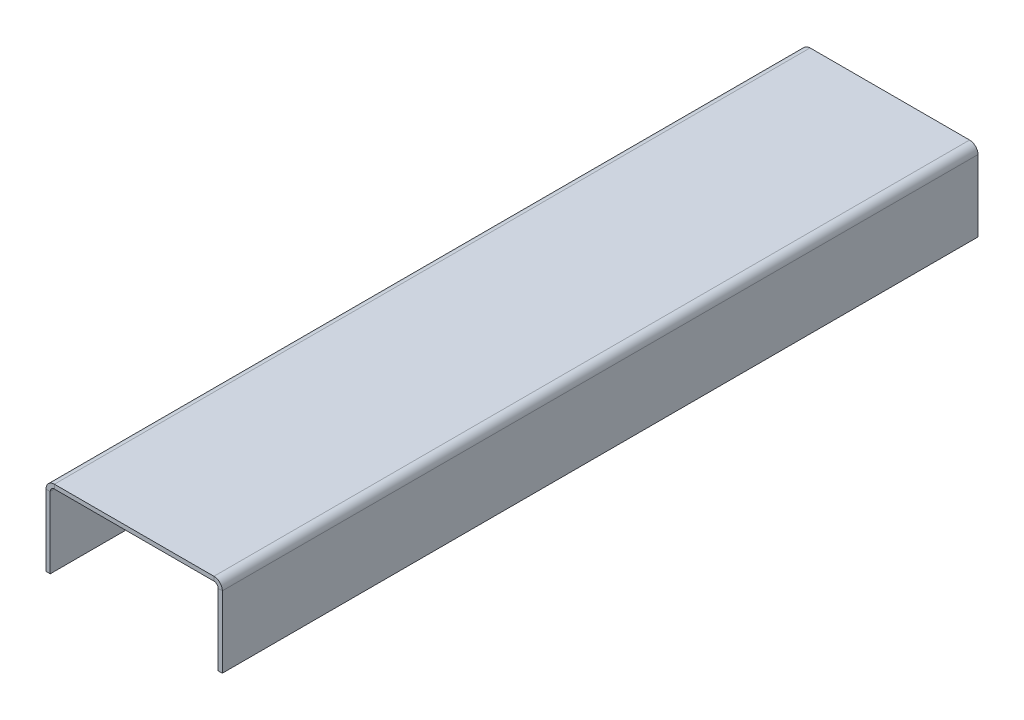
SolidWorks part; units mm, degrees
note: The reader was unsure of these and kept them because the rebuilt part matched: thickness of "Base-Flange1", "Edge-Flange1", "Sheet-Metal1", "Sheet-Metal2"; flange length of "Edge-Flange1".
material "6061 Alloy"
ref_plane "Front Plane" through (0, 0, 0) normal (0, 0, 1) x (1, 0, 0)
ref_plane "Top Plane" through (0, 0, 0) normal (0, 1, 0) x (1, 0, 0)
ref_plane "Right Plane" through (0, 0, 0) normal (1, 0, 0) x (0, 0, -1)
sketch "Front View Skeleton" plane through (0, 0, 0) normal (0, 0, 1) x (1, 0, 0)
  line L0 (-40, 240) -> (40, 240)
  line L1 (40, 240) -> (42, 240)
  line L2 (42, 240) -> (42, 30)
  line L3 (42, 30) -> (40, 30)
  line L4 (40, 30) -> (40, 240)
  line L5 (40, 240) -> (40, 242)
  line L6 (40, 242) -> (-40, 242)
  line L7 (0, 242) -> (0, 240) construction
  line L8 (0, 240) -> (0, 0) construction
  line L9 (-40, 240) -> (-40, 242)
  line L10 (-40, 30) -> (-40, 240)
  line L11 (-42, 30) -> (-40, 30)
  line L12 (-42, 240) -> (-42, 30)
  line L13 (-40, 240) -> (-42, 240)
  line L14 (42, 30) -> (42, 28)
  line L38 (34.8453, 358) -> (100, 245.1487)
  line L39 (-36, 360) -> (36, 360)
  line L41 (-34.8453, 358) -> (34.8453, 358)
  line L43 (-36, 360) -> (34.8453, 358) construction
  line L44 (-34.8453, 358) -> (36, 360) construction
  line L45 (232.6917, 28) -> (232.6917, 388) construction
  line L46 (36, 360) -> (36.5774, 359)
  line L47 (101.7321, 246.1487) -> (36.5774, 359)
  line L50 (42, 28) -> (96, 28)
  line L51 (-101.7321, 246.1487) -> (-36.5774, 359)
  line L52 (-34.8453, 358) -> (-100, 245.1487)
  line L53 (96, 28) -> (100, 28)
  line L54 (100, 28) -> (100, 46)
  line L55 (100, 46) -> (98, 46)
  line L56 (98, 46) -> (98, 30)
  line L58 (0, 358) -> (0, 360) construction
  line L59 (-36.5774, 359) -> (-36, 360)
  line L60 (-101.7321, 246.1487) -> (-100, 245.1487) construction
  line L66 (98, 30) -> (42, 30)
  line L72 (-42, 30) -> (-42, 28)
  line L73 (101.7321, 246.1487) -> (102, 245.6846)
  line L74 (-102, 245.6846) -> (-101.7321, 246.1487)
  line L75 (34.8453, 358) -> (36.5774, 359) construction
  line L77 (100, 28) -> (100, 245.1487)
  line L81 (-98, 30) -> (-42, 30)
  line L82 (-98, 46) -> (-98, 30)
  line L83 (-100, 46) -> (-98, 46)
  line L84 (-100, 28) -> (-100, 46)
  line L85 (-96, 28) -> (-100, 28)
  line L86 (-42, 28) -> (-96, 28)
  line L87 (100, 28) -> (102, 28)
  line L88 (-100, 28) -> (-97.9629, 28)
  line L89 (102, 245.6846) -> (102, 28)
  line L90 (-102, 245.6846) -> (-102, 28)
  line L91 (-100, 28) -> (-100, 245.1487)
  line L92 (-100, 28) -> (-102, 28)
  point P33 (0, 358.9837)
ref_plane "Plane1" through (0, 240, 0) normal (0, 1, 0) x (1, 0, 0)
sketch "Sketch1" plane through (0, 240, 0) normal (0, 1, 0) x (1, 0, 0)
  line L1 (-40, 180) -> (40, 180)
  line L2 (-40, 180) -> (-40, -180)
  line L3 (-40, -180) -> (40, -180)
  line L4 (40, 180) -> (40, -180)
  line L5 (-40, 180) -> (40, -180) construction
  line L6 (-40, -180) -> (40, 180) construction
  point P0 (0, 0)
base flange "Base-Flange1" sketch "Sketch1" thickness 2 reverse thickness direction yes parameters "D1"=2
edge flange "Edge-Flange1" sketch "Sketch8" flange profiles "Sketch8", "Sketch10" flange angle 90 flange length 36 flange position material outside bend radius 2 thickness 2 relief obround parameters "D6"=10, "D8"=1
sketch "Sketch8" plane through (40, 240, 0) normal (1, 0, 0) x (0, 0, 1)
  line L2 (-180, 0) -> (-180, 36)
  line L3 (-180, 36) -> (180, 36)
  line L4 (180, 36) -> (180, 0)
  line L11 (180, 0) -> (-180, 0) construction
  line L12 (180, 0) -> (-180, 0)
sketch "Sketch10" plane through (-40, 240, 0) normal (-1, 0, 0) x (0, 0, -1)
  line L2 (-180, 0) -> (-180, 36)
  line L3 (-180, 36) -> (180, 36)
  line L4 (180, 36) -> (180, 0)
  line L11 (180, 0) -> (-180, 0) construction
  line L12 (180, 0) -> (-180, 0)
bend "EdgeBend1" bend radius 2 bend angle 90 parameters "D5"=1
bend "EdgeBend2" bend radius 2 bend angle 90 parameters "D5"=3
sketch "Bend-Lines1" [suppressed] plane through (0, 0, 0) normal (0, 1, 0) x (1, 0, 0)
sketch "Bounding-Box1" [suppressed] plane through (0, 0, 0) normal (0, 1, 0) x (1, 0, 0)
sheet metal parameters "Sheet-Metal1" thickness 2 parameters "D1"=2
flat pattern "Flat-Pattern1" [suppressed]
sketch "Bend-Lines2" plane through (0, 0, 0) normal (0, 1, 0) x (1, 0, 0)
sketch3d "Bounding-Box2" [suppressed]
  line L0 (40, 180, 0) -> (40, -180, 0) construction
  line L1 (-40, 180, 0) -> (-40, -180, 0) construction
  line L2 (40, 180, 0) -> (-40, 180, 0) construction
  line L3 (40, -180, 0) -> (-40, -180, 0) construction
sheet metal parameters "Sheet-Metal2" thickness 2 parameters "D1"=2, "D7"=3
flat pattern "Flat-Pattern1"
sketch "Bend-Lines2" plane through (0, 240, 0) normal (0, -1, 0) x (-1, 0, 0)
  line L0 (-40.3562, 180) -> (-40.3562, -180) construction
  line L1 (-40.3562, 180) -> (-40.3562, -180) construction
  line L2 (40.3562, -180) -> (40.3562, 180) construction
  line L3 (40.3562, -180) -> (40.3562, 180) construction
sketch3d "Bounding-Box2" [suppressed]
  line L0 (76.7124, 180, 0) -> (76.7124, -180, 0) construction
  line L1 (-76.7124, 180, 0) -> (-76.7124, -180, 0) construction
  line L2 (76.7124, 180, 0) -> (-76.7124, 180, 0) construction
  line L3 (76.7124, -180, 0) -> (-76.7124, -180, 0) construction
bend of the flat pattern "Flatten-<EdgeBend1>1"
bend of the flat pattern "Flatten-<EdgeBend2>1"
